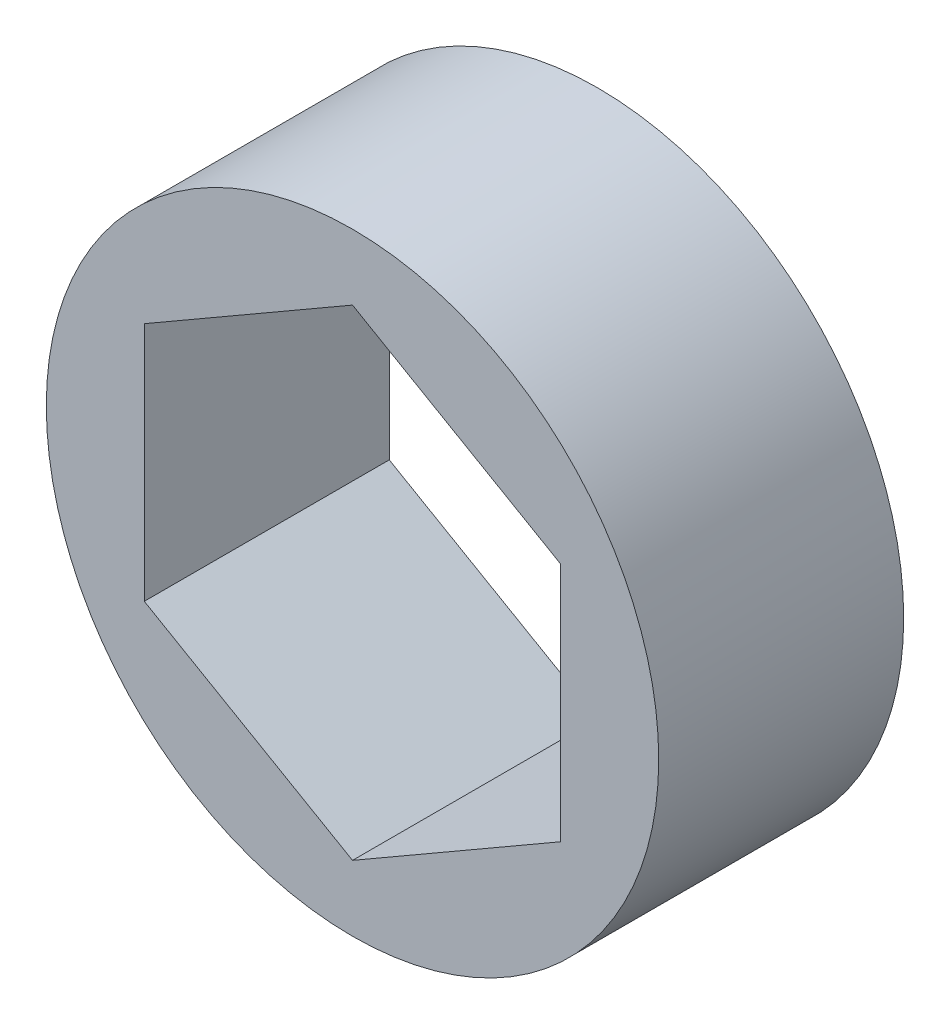
SolidWorks part; units mm, degrees
material "PET"
ref_plane "Front" through (0, 0, 0) normal (0, 0, 1) x (1, 0, 0)
ref_plane "Top" through (0, 0, 0) normal (0, 1, 0) x (1, 0, 0)
ref_plane "Right" through (0, 0, 0) normal (1, 0, 0) x (0, 0, -1)
sketch "Sketch1" plane through (0, 0, 0) normal (0, 0, 1) x (1, 0, 0)
  line L1 (0, 7.479) -> (-6.477, 3.7395)
  line L2 (-6.477, 3.7395) -> (-6.477, -3.7395)
  line L3 (-6.477, -3.7395) -> (0, -7.479)
  line L4 (0, -7.479) -> (6.477, -3.7395)
  line L5 (6.477, -3.7395) -> (6.477, 3.7395)
  line L6 (6.477, 3.7395) -> (0, 7.479)
  circle A0 centre (0, 0) radius 9.525
  circle A1 centre (0, 0) radius 6.477 construction
  dimension "D2" = 19.05
  dimension "D1" = 12.954
extrude "Boss-Extrude1" add sketch "Sketch1" along normal blind 7.62
